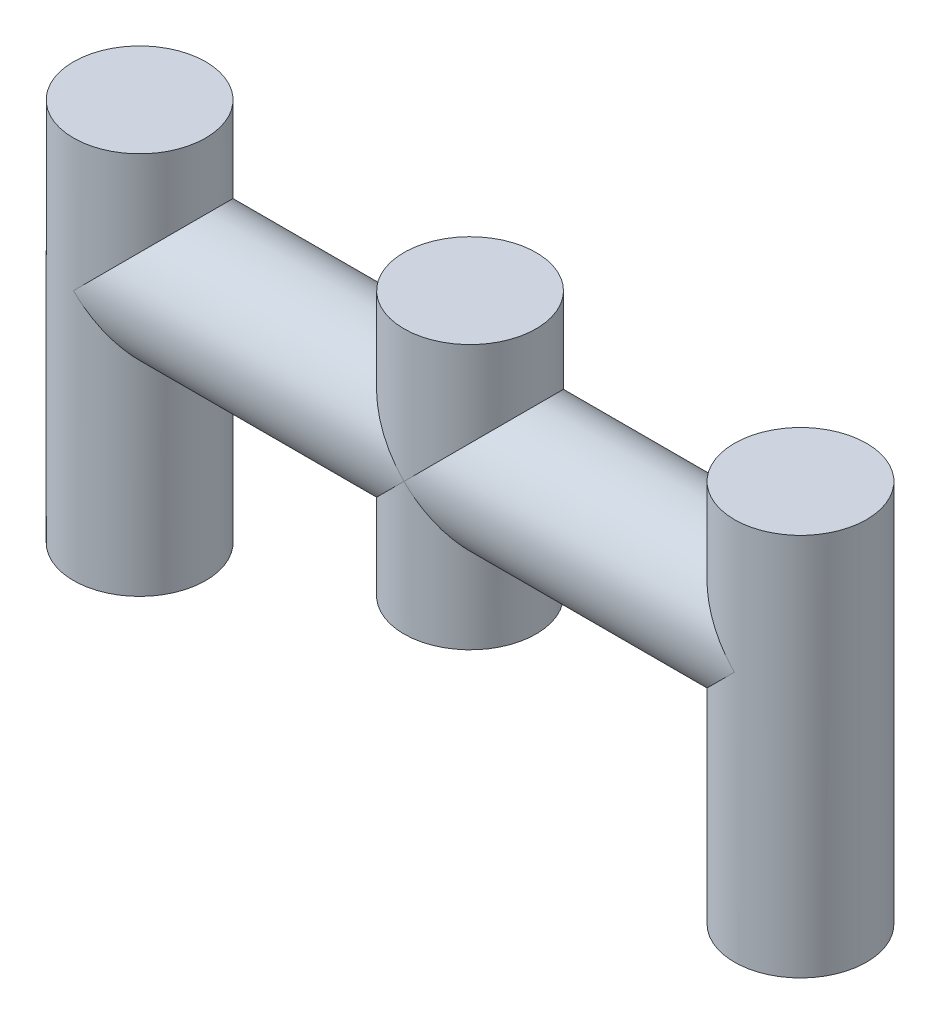
SolidWorks part; units mm, degrees
ref_plane "Front Plane" through (0, 0, 0) normal (0, 0, 1) x (1, 0, 0)
ref_plane "Top Plane" through (0, 0, 0) normal (0, 1, 0) x (1, 0, 0)
ref_plane "Right Plane" through (0, 0, 0) normal (1, 0, 0) x (0, 0, -1)
sketch "Sketch2" plane through (0, 0, 0) normal (0, 1, 0) x (1, 0, 0)
  circle A0 centre (0, 0) radius 2.5
  dimension "D1" = 5
extrude "Boss-Extrude2" add sketch "Sketch2" along normal blind 10
sketch "Sketch3" plane through (0, 0, 0) normal (1, 0, 0) x (0, 0, -1)
  line L0 (0, 0) -> (0, 10) construction
  line L1 (2.5, 10) -> (-2.5, 10) construction
  line L2 (-2.5, 5) -> (2.5, 5) construction
  line L3 (-2.5, 10) -> (-2.5, 0) construction
  line L4 (2.5, 0) -> (2.5, 10) construction
  circle A0 centre (0, 5) radius 2.5
  dimension "D1" = 5
extrude "Boss-Extrude3" add sketch "Sketch3" along normal blind 12.5
sketch "Sketch4" plane through (0, 0, 0) normal (0, 1, 0) x (1, 0, 0)
  line L0 (12.5, -2.5) -> (12.5, 2.5) construction
  line L1 (12.5, 2.5) -> (12.5, -2.5)
  arc A0 (12.5, 2.5) -> (12.5, -2.5) centre (12.5, 0) ccw
extrude "Boss-Extrude4" add sketch "Sketch4" along normal blind 10
mirror "Mirror5" about plane through (12.5, 5, 0) normal (1, 0, 0) of "Boss-Extrude4", "Boss-Extrude3", "Boss-Extrude2"
sketch "Sketch5" plane through (0, 0, 0) normal (0, -1, 0) x (1, 0, 0)
  circle A0 centre (0, 0) radius 2.5
  circle A1 centre (25, 0) radius 2.5
extrude "Boss-Extrude5" add sketch "Sketch5" along normal blind 4.5
